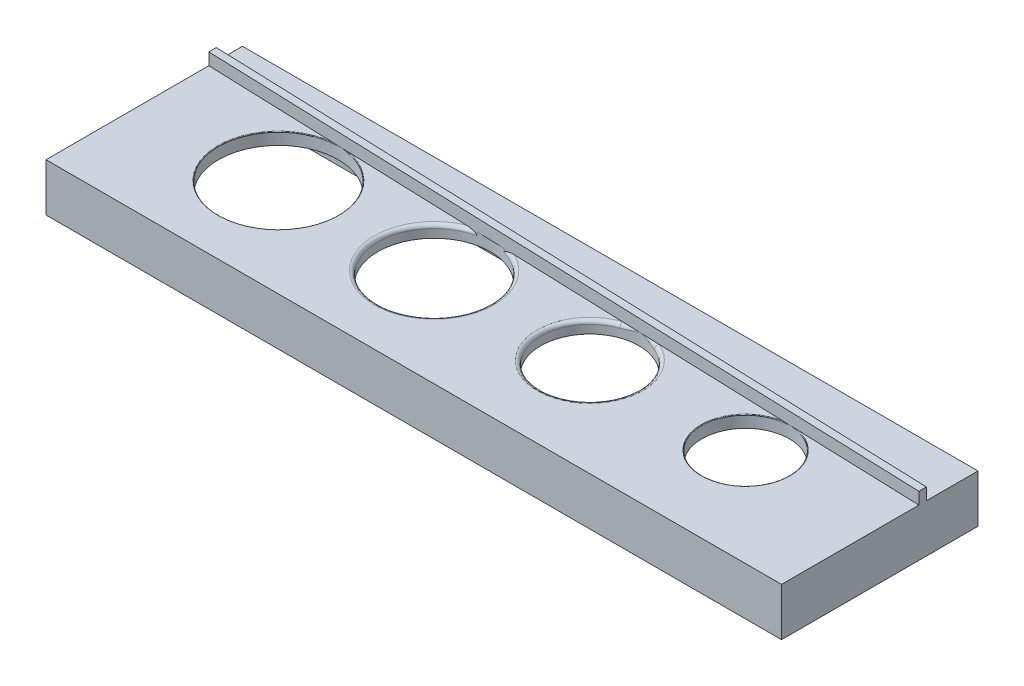
SolidWorks part; units mm, degrees
ref_plane "Front Plane" through (0, 0, 0) normal (0, 0, 1) x (1, 0, 0)
ref_plane "Top Plane" through (0, 0, 0) normal (0, 1, 0) x (1, 0, 0)
ref_plane "Right Plane" through (0, 0, 0) normal (1, 0, 0) x (0, 0, -1)
sketch "Sketch1" plane through (0, 0, 0) normal (0, 1, 0) x (1, 0, 0)
  line L1 (-52.7378, 9.3227) -> (103.2182, 9.3227)
  line L2 (-52.7378, 9.3227) -> (-52.7378, -32.3333)
  line L3 (-52.7378, -32.3333) -> (103.2182, -32.3333)
  line L4 (103.2182, 9.3227) -> (103.2182, -32.3333)
  dimension "D1" = 155.956
  dimension "D2" = 41.656
extrude "Boss-Extrude1" add sketch "Sketch1" along normal blind 2.54
sketch "Sketch2" plane through (0, 0, 0) normal (0, -1, 0) x (-1, 0, 0)
  line L0 (52.7378, -32.3333) -> (-103.2182, -32.3333) construction
  line L1 (51.1503, -30.7458) -> (-101.6307, -30.7458)
  line L2 (51.1503, -30.7458) -> (51.1503, 7.7352)
  line L3 (51.1503, 7.7352) -> (-101.6307, 7.7352)
  line L4 (-101.6307, -30.7458) -> (-101.6307, 7.7352)
  line L5 (-103.2182, 9.3227) -> (52.7378, 9.3227) construction
  line L6 (52.7378, 9.3227) -> (52.7378, -32.3333) construction
  line L7 (-103.2182, -32.3333) -> (-103.2182, 9.3227) construction
  line L9 (52.7378, -32.3333) -> (-103.2182, -32.3333)
  line L10 (52.7378, -32.3333) -> (52.7378, 9.3227)
  line L11 (52.7378, 9.3227) -> (-103.2182, 9.3227)
  line L12 (-103.2182, -32.3333) -> (-103.2182, 9.3227)
  dimension "D1" = 1.5875
  dimension "D2" = 1.5875
  dimension "D3" = 1.5875
  dimension "D4" = 1.5875
extrude "Boss-Extrude2" add sketch "Sketch2" along normal blind 7.62
sketch "Sketch3" plane through (0, 2.54, 0) normal (0, 1, 0) x (1, 0, 0)
  line L0 (-52.7378, -11.5053) -> (103.2182, -11.5053) construction
  line L1 (-52.7378, 9.3227) -> (-52.7378, -32.3333) construction
  line L2 (103.2182, -32.3333) -> (103.2182, 9.3227) construction
  circle A0 centre (74.7702, -11.5053) radius 9.271
  circle A1 centre (-24.2898, -11.5053) radius 12.7
  circle A2 centre (41.7502, -11.5053) radius 10.414
  circle A3 centre (8.7302, -11.5053) radius 11.938
  dimension "D1" = 18.542
  dimension "D2" = 25.4
  dimension "D3" = 20.828
  dimension "D4" = 23.876
  dimension "D5" = 33.02
  dimension "D6" = 28.448
  dimension "D7" = 33.02
  dimension "D8" = 33.02
  dimension "D9" = 28.448
extrude "Cut-Extrude1" cut sketch "Sketch3" against normal blind 2.54
sketch "Sketch4" plane through (0, 2.54, 0) normal (0, 1, 0) x (1, 0, 0)
  line L1 (-52.7378, 3.7761) -> (103.2182, -1.6256)
  line L2 (-52.7378, 3.7761) -> (-52.7378, 2.1877)
  line L3 (-52.7378, 2.1877) -> (103.2182, -3.214)
  line L4 (103.2182, -1.6256) -> (103.2182, -3.214)
  line L5 (-52.7378, 9.3227) -> (-52.7378, -32.3333) construction
  line L6 (103.2182, -32.3333) -> (103.2182, 9.3227) construction
  circle A11 centre (-24.2898, -11.5053) radius 12.7 construction
  circle A12 centre (74.7702, -11.5053) radius 9.271 construction
  dimension "D1" = 1.5875
extrude "Boss-Extrude3" add sketch "Sketch4" along normal blind 2.54
fillet "Fillet3" radius 0.762 2 edges at (41.7502, 2.54, 21.9193) (8.317, 2.54, 23.4361)
fillet "Fillet4" radius 0.127 2 edges at (74.7702, 2.54, 20.7763) (-24.2898, 2.54, 24.2053)
